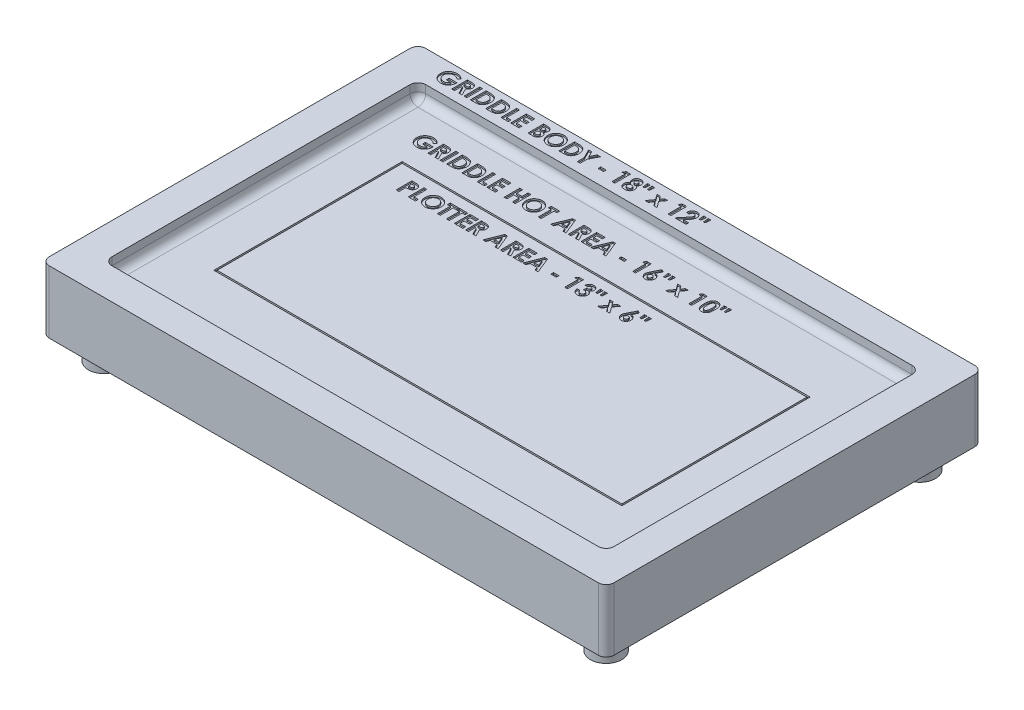
SolidWorks part; units mm, degrees
ref_plane "Front Plane" through (0, 0, 0) normal (0, 0, 1) x (1, 0, 0)
ref_plane "Top Plane" through (0, 0, 0) normal (0, 1, 0) x (1, 0, 0)
ref_plane "Right Plane" through (0, 0, 0) normal (1, 0, 0) x (0, 0, -1)
sketch "Sketch2" plane through (0, 0, 0) normal (0, 1, 0) x (1, 0, 0)
  line L1 (-228.6, 0) -> (228.6, 0)
  line L2 (-228.6, 0) -> (-228.6, 304.8)
  line L3 (-228.6, 304.8) -> (228.6, 304.8)
  line L4 (228.6, 0) -> (228.6, 304.8)
  point P4 (0, 0)
  dimension "D1" = 304.8
  dimension "D2" = 457.2
extrude "Boss-Extrude1" add sketch "Sketch2" along normal blind 50.8
sketch "Sketch3" plane through (0, 0, 0) normal (0, -1, 0) x (1, 0, 0)
  line L0 (-228.6, 0) -> (228.6, 0) construction
  line L1 (-203.2, -25.4) -> (203.2, -25.4) construction
  line L2 (-203.2, -25.4) -> (-203.2, -279.4) construction
  line L3 (-203.2, -279.4) -> (203.2, -279.4) construction
  line L4 (203.2, -25.4) -> (203.2, -279.4) construction
  line L5 (228.6, -304.8) -> (-228.6, -304.8) construction
  line L6 (-228.6, -304.8) -> (-228.6, 0) construction
  line L7 (228.6, 0) -> (228.6, -304.8) construction
  circle A0 centre (-203.2, -25.4) radius 12.7
  circle A1 centre (-203.2, -279.4) radius 12.7
  circle A2 centre (203.2, -279.4) radius 12.7
  circle A3 centre (203.2, -25.4) radius 12.7
  dimension "D5" = 25.4
  dimension "D1" = 25.4
  dimension "D2" = 25.4
  dimension "D3" = 25.4
  dimension "D4" = 25.4
extrude "Boss-Extrude2" add sketch "Sketch3" along normal blind 19.05 contours A1 | A3 | A0 | A2 region at (-203.2, 0, -25.4) region at (-203.2, 0, -279.4) region at (203.2, 0, -25.4)
sketch "Sketch4" plane through (0, 50.8, 0) normal (0, 1, 0) x (1, 0, 0)
  line L0 (-228.6, 304.8) -> (-228.6, 0) construction
  line L1 (-203.2, 279.4) -> (203.2, 279.4)
  line L2 (-203.2, 279.4) -> (-203.2, 25.4)
  line L3 (-203.2, 25.4) -> (203.2, 25.4)
  line L4 (203.2, 279.4) -> (203.2, 25.4)
  point P4 (0, 25.4)
  point P8 (-228.6, 152.4)
  point P9 (-203.2, 152.4)
  dimension "D1" = 406.4
  dimension "D2" = 254
extrude "Cut-Extrude1" cut sketch "Sketch4" against normal blind 12.7
sketch "Sketch5" plane through (0, 38.1, 0) normal (0, 1, 0) x (1, 0, 0)
  line L0 (-228.6, 304.8) -> (-228.6, 0) construction
  line L1 (-165.1, 228.6) -> (165.1, 228.6)
  line L2 (-165.1, 228.6) -> (-165.1, 76.2)
  line L3 (-165.1, 76.2) -> (165.1, 76.2)
  line L4 (165.1, 228.6) -> (165.1, 76.2)
  line L5 (-163.83, 227.33) -> (163.83, 227.33)
  line L6 (-163.83, 227.33) -> (-163.83, 77.47)
  line L7 (-163.83, 77.47) -> (163.83, 77.47)
  line L8 (163.83, 227.33) -> (163.83, 77.47)
  point P8 (0, 77.47)
  point P9 (0, 76.2)
  point P13 (-228.6, 152.4)
  point P14 (-165.1, 152.4)
  point P15 (-163.83, 152.4)
  dimension "D1" = 152.4
  dimension "D2" = 330.2
  dimension "D3" = 1.27
  dimension "D4" = 1.27
extrude "Cut-Extrude2" cut sketch "Sketch5" against normal blind 1.27
fillet "Fillet1" radius 6.35 12 edges at (203.2, 44.45, -25.4) (-203.2, 44.45, -279.4) (-203.2, 38.1, -152.4) (0, 38.1, -25.4) (-203.2, 44.45, -25.4) (203.2, 38.1, -152.4) (0, 38.1, -279.4) (203.2, 44.45, -279.4) (228.6, 25.4, -304.8) (228.6, 25.4, 0) (-228.6, 25.4, -304.8) (-228.6, 25.4, 0)
sketch "Sketch6" plane through (0, 50.8, 0) normal (0, 1, 0) x (1, 0, 0)
  text T0 "GRIDDLE BODY - 18\" x 12\"" font "Century Gothic" height 12.7
extrude "Cut-Extrude3" cut sketch "Sketch6" against normal blind 1.27
sketch "Sketch7" plane through (0, 38.1, 0) normal (0, 1, 0) x (1, 0, 0)
  text T0 "GRIDDLE HOT AREA - 16\" x 10\"" font "Century Gothic" height 12.7
extrude "Cut-Extrude4" cut sketch "Sketch7" against normal blind 1.27
sketch "Sketch8" plane through (0, 38.1, 0) normal (0, 1, 0) x (1, 0, 0)
  text T0 "PLOTTER AREA - 13\" x 6\"" font "Century Gothic" height 12.7
extrude "Cut-Extrude5" cut sketch "Sketch8" against normal blind 1.27
